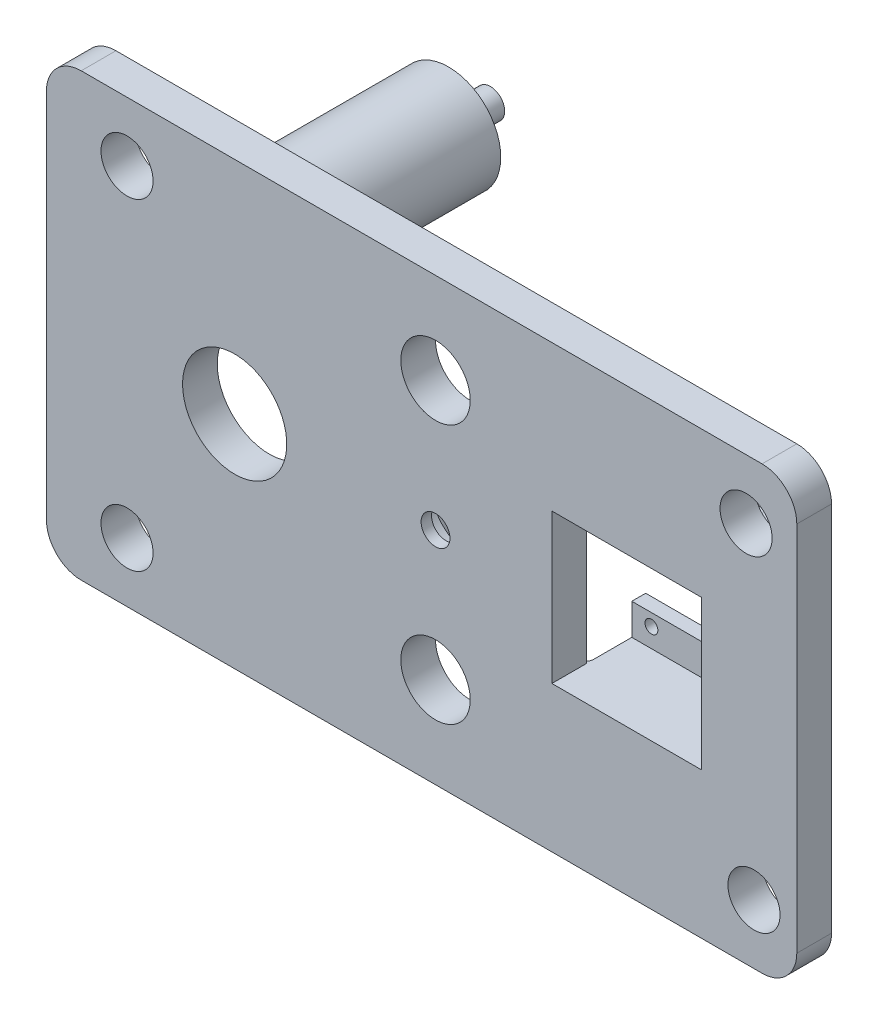
SolidWorks part; units mm, degrees
ref_plane "Front Plane" through (0, 0, 0) normal (0, 0, 1) x (1, 0, 0)
ref_plane "Top Plane" through (0, 0, 0) normal (0, 1, 0) x (1, 0, 0)
ref_plane "Right Plane" through (0, 0, 0) normal (1, 0, 0) x (0, 0, -1)
sketch "Sketch1" plane through (0, 0, 0) normal (0, 0, 1) x (1, 0, 0)
  line L1 (-108, 63.5) -> (108, 63.5)
  line L2 (-108, 63.5) -> (-108, -63.5)
  line L3 (-108, -63.5) -> (108, -63.5)
  line L4 (108, 63.5) -> (108, -63.5)
  line L5 (-108, 63.5) -> (108, -63.5) construction
  line L6 (-108, -63.5) -> (108, 63.5) construction
  point P0 (0, 0)
  dimension "D1" = 127
  dimension "D2" = 216
extrude "Boss-Extrude1" add sketch "Sketch1" along normal blind 10
fillet "Fillet1" radius 10 1 edges at (-108, 63.5, 5)
fillet "Fillet2" radius 10 3 edges at (-108, -63.5, 5) (108, 63.5, 5) (108, -63.5, 5)
sketch "Sketch9" plane through (0, 0, 0) normal (0, 0, -1) x (-1, 0, 0)
  line L0 (-98, 63.5) -> (98, 63.5) construction
  line L1 (-37.5, -21.5) -> (-80.5, -21.5)
  line L2 (-37.5, -21.5) -> (-37.5, 21.5)
  line L3 (-37.5, 21.5) -> (-80.5, 21.5)
  line L4 (-80.5, -21.5) -> (-80.5, 21.5)
  line L5 (-37.5, -21.5) -> (-80.5, 21.5) construction
  line L6 (-37.5, 21.5) -> (-80.5, -21.5) construction
  line L8 (108, 0) -> (-108, 0) construction
  line L9 (108, 53.5) -> (108, -53.5) construction
  line L10 (-108, -53.5) -> (-108, 53.5) construction
  circle A0 centre (-4, 0) radius 11.15
  point P2 (-59, 0)
  dimension "D6" = 22.3
  dimension "D1" = 27.5
  dimension "D2" = 55
  dimension "D3" = 43
  dimension "D4" = 43
  dimension "D5" = 63.5
extrude "Cut-Extrude4" cut sketch "Sketch9" against normal blind 7 contours A0
sketch "Sketch12" plane through (0, 0, 7) normal (0, 0, -1) x (-1, 0, 0)
  circle A0 centre (-4, 0) radius 4.15
  dimension "D1" = 8.3
extrude "Cut-Extrude5" cut sketch "Sketch12" against normal blind 7
extrude "Cut-Extrude6" cut sketch "Sketch9<4>" against normal through all contours L3 L4 L1 L2
sketch "Sketch9<4>" plane through (0, 0, 0) normal (0, 0, -1) x (-1, 0, 0) same geometry as "Sketch9"
sketch "Sketch13" plane through (0, 0, 0) normal (0, 0, -1) x (-1, 0, 0)
  line L1 (-37.5, -21.5) -> (-80.5, -21.5)
  line L2 (-37.5, -21.5) -> (-37.5, -25.5)
  line L3 (-37.5, -25.5) -> (-80.5, -25.5)
  line L4 (-80.5, -21.5) -> (-80.5, -25.5)
  dimension "D1" = 4
  dimension "D2" = 43
extrude "Boss-Extrude2" add sketch "Sketch13" along normal blind 17
ref_plane "Plane3" through (0, -21.5, 0) normal (0, 1, 0) x (1, 0, 0)
ref_plane "Plane4" through (0, 0, 0) normal (0, 0, -1) x (-1, 0, 0)
ref_plane "Plane6" through (80.5, 0, 0) normal (1, 0, 0) x (0, 0, -1)
sketch "Sketch16" plane through (80.5, 0, 0) normal (1, 0, 0) x (0, 0, -1)
  line L0 (17, -21.5) -> (0, -21.5) construction
  line L1 (17.0075, -21.5) -> (0.1109, -21.5)
  line L2 (17.0075, -21.5) -> (17.0075, -25.5)
  line L3 (17.0075, -25.5) -> (0.1109, -25.5)
  line L4 (0.1109, -21.5) -> (0.1109, -25.5)
  line L5 (17, -25.5) -> (0, -25.5) construction
fillet "Fillet4" radius 2 3 edges at (59, -25.5, 0) (37.5, -23.5, 0) (80.5, -23.5, 0)
sketch "Sketch17" plane through (0, -21.5, 0) normal (0, 1, 0) x (1, 0, 0)
  line L0 (80.5, 17.0075) -> (80.5, 0.1109) construction
  line L1 (37.5, 17) -> (80.5, 17)
  line L2 (37.5, 17) -> (37.5, 13)
  line L3 (37.5, 13) -> (80.5, 13)
  line L4 (80.5, 17) -> (80.5, 13)
  dimension "D1" = 4
extrude "Boss-Extrude5" add sketch "Sketch17" along normal blind 9
sketch "Sketch18" plane through (0, 0, 0) normal (0, 0, -1) x (-1, 0, 0)
  line L1 (-37.5, 21.5) -> (-80.5, 21.5)
  line L2 (-37.5, 21.5) -> (-37.5, 25.5)
  line L3 (-37.5, 25.5) -> (-80.5, 25.5)
  line L4 (-80.5, 21.5) -> (-80.5, 25.5)
  dimension "D1" = 43
  dimension "D2" = 4
extrude "Boss-Extrude6" add sketch "Sketch18" along normal blind 17
ref_plane "Plane7" through (0, 21.5, 0) normal (0, -1, 0) x (-1, 0, 0)
sketch "Sketch19" plane through (0, 21.5, 0) normal (0, -1, 0) x (-1, 0, 0)
  line L0 (-80.5, 17) -> (-80.5, 0) construction
  line L1 (-37.5, 17) -> (-80.5, 17)
  line L2 (-37.5, 17) -> (-37.5, 13)
  line L3 (-37.5, 13) -> (-80.5, 13)
  line L4 (-80.5, 17) -> (-80.5, 13)
  dimension "D1" = 4
extrude "Boss-Extrude7" add sketch "Sketch19" along normal blind 9
fillet "Fillet5" radius 2 3 edges at (37.5, 23.5, 0) (80.5, 23.5, 0) (59, 25.5, 0)
ref_plane "Plane8" through (0, 0, -17) normal (0, 0, -1) x (-1, 0, 0)
sketch "Sketch20" plane through (0, 0, -17) normal (0, 0, -1) x (-1, 0, 0)
  line L0 (-37.5, -25.5) -> (-37.5, -12.5) construction
  line L2 (-80.5, -21.5) -> (-37.5, -21.5)
  line L3 (-80.5, -12.5) -> (-80.5, -25.5) construction
  line L4 (-80.5, -12.5) -> (-37.5, -12.5) construction
  circle A0 centre (-43.15, -16) radius 1.85
  circle A1 centre (-74.85, -16) radius 1.85
  dimension "D3" = 5.5
  dimension "D4" = 3.7
  dimension "D5" = 5.65
  dimension "D6" = 3.7
  dimension "D1" = 5.65
  dimension "D2" = 9
extrude "Cut-Extrude7" cut sketch "Sketch20" against normal blind 9 contours A1 | A0
ref_plane "Plane9" through (0, 0, -17) normal (0, 0, -1) x (-1, 0, 0)
sketch "Sketch23" plane through (0, 0, -17) normal (0, 0, -1) x (-1, 0, 0)
  line L0 (-37.5, 21.5) -> (-80.5, 21.5)
  line L1 (-37.5, 12.5) -> (-37.5, 25.5) construction
  line L2 (-80.5, 25.5) -> (-80.5, 12.5) construction
  line L3 (-37.5, 12.5) -> (-80.5, 12.5) construction
  circle A0 centre (-43.15, 15.85) radius 1.85
  circle A1 centre (-74.85, 16) radius 1.85
  dimension "D4" = 3.7
  dimension "D5" = 3.7
  dimension "D6" = 5.65
  dimension "D7" = 5.65
  dimension "D1" = 9
  dimension "D2" = 5.5
  dimension "D3" = 5.65
extrude "Cut-Extrude8" cut sketch "Sketch23" against normal blind 9 contours A0 | A1
ref_plane "Plane10" through (0, 0, 0) normal (0, 0, -1) x (-1, 0, 0)
sketch "Sketch25" plane through (0, 0, 0) normal (0, 0, -1) x (-1, 0, 0)
  line L0 (5.8491, 5.5555) -> (-13.7116, -5.4779)
  line L1 (-4, -11.15) -> (-4, 11.15)
  line L2 (98, -63.5) -> (-98, -63.5) construction
  line L3 (-98, 63.5) -> (98, 63.5) construction
  circle A0 centre (5.8491, 5.5555) radius 0.0422
  circle A1 centre (-4, 0) radius 11.15 construction
  circle A2 centre (51.0687, -43.5) radius 15
  circle A3 centre (51.0687, 43.5) radius 15
  point P8 (-3.9313, 0.0388)
  dimension "D4" = 20
  dimension "D5" = 30
  dimension "D6" = 30
  dimension "D1" = 55
  dimension "D2" = 55
  dimension "D3" = 20
extrude "Boss-Extrude9" add sketch "Sketch25" along normal blind 48.84 contours A3 | A2
ref_plane "Plane11" through (0, 0, -48.84) normal (0, 0, -1) x (-1, 0, 0)
sketch "Sketch26" plane through (0, 0, -48.84) normal (0, 0, -1) x (-1, 0, 0)
  circle A0 centre (51.0687, -43.5) radius 4.15
  dimension "D1" = 8.3
extrude "Boss-Extrude10" add sketch "Sketch26" along normal blind 12
ref_plane "Plane12" through (0, 0, -48.84) normal (0, 0, -1) x (-1, 0, 0)
sketch "Sketch27" plane through (0, 0, -48.84) normal (0, 0, -1) x (-1, 0, 0)
  circle A0 centre (51.0687, 43.5) radius 4.15
  dimension "D1" = 8.3
extrude "Boss-Extrude11" add sketch "Sketch27" along normal blind 12
fillet "Fillet9" radius 2 1 edges at (-36.0687, -43.5, 0)
fillet "Fillet10" radius 2 1 edges at (-36.0687, 43.5, 0)
ref_plane "Plane13" through (0, 0, 10) normal (0, 0, 1) x (1, 0, 0)
sketch "Sketch28" plane through (0, 0, 10) normal (0, 0, 1) x (1, 0, 0)
  line L0 (98, 63.5) -> (-98, 63.5) construction
  line L3 (-98, -63.5) -> (98, -63.5) construction
  circle A0 centre (-84.8117, 46.37) radius 7.5
  circle A1 centre (-84.8117, -46.37) radius 7.5
  circle A2 centre (95.674, -46.3698) radius 7.5
  circle A3 centre (93.3991, 46.37) radius 7.5
  dimension "D2" = 15
  dimension "D3" = 17.13
  dimension "D4" = 15
  dimension "D5" = 17.13
  dimension "D6" = 15
  dimension "D7" = 15
  dimension "D1" = 17.13
extrude "Cut-Extrude9" cut sketch "Sketch28" against normal through all
ref_plane "Plane14" through (0, 0, 0) normal (0, 0, -1) x (-1, 0, 0)
sketch "Sketch29" plane through (0, 0, 0) normal (0, 0, -1) x (-1, 0, 0)
  line L0 (-108, 0) -> (108, 0) construction
  line L1 (-108, -53.5) -> (-108, 53.5) construction
  line L2 (108, 53.5) -> (108, -53.5) construction
  line L3 (-4, -11.15) -> (-4, -63.5) construction
  line L5 (98, -63.5) -> (-98, -63.5) construction
  line L7 (-4, 11.15) -> (-4, 63.5) construction
  line L8 (-98, 63.5) -> (98, 63.5) construction
  circle A5 centre (-4, 0) radius 11.15 construction
  circle A6 centre (-4, 0) radius 11.15 construction
  circle A7 centre (-4, 37.325) radius 10
  circle A8 centre (53.8283, 0) radius 15
  circle A9 centre (-4, -37.325) radius 10
  point P24 (0, 0)
  dimension "D1" = 20
  dimension "D2" = 30
extrude "Cut-Extrude10" cut sketch "Sketch29" against normal through all contours A8 | A9 | A7 region at (-53.8283, 0, 0) region at (4, -37.325, 0)
